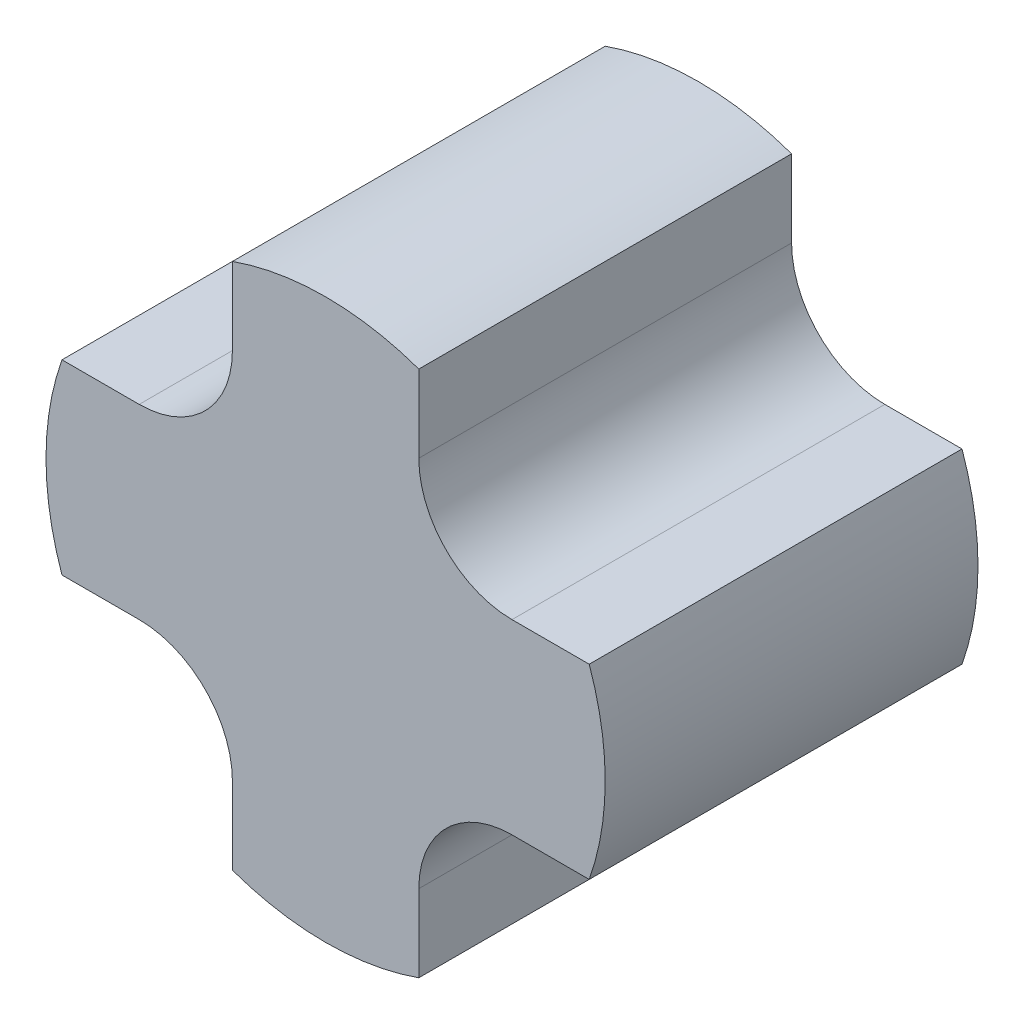
SolidWorks part; units mm, degrees
ref_plane "Front Plane" through (0, 0, 0) normal (1, 0, 0) x (0, 1, 0)
ref_plane "Top Plane" through (0, 0, 0) normal (0, 0, 1) x (0, 1, 0)
ref_plane "Right Plane" through (0, 0, 0) normal (0, 1, 0) x (-1, 0, 0)
sketch "Sketch1" plane through (0, 0, 0) normal (0, 0, 1) x (0, 1, 0)
  line L1 (-50, 141.4214) -> (-50, 0)
  line L2 (50, 141.4214) -> (50, 0)
  line L3 (-50, 0) -> (50, 0)
  arc A0 (50, 141.4214) -> (-50, 141.4214) centre (0, 0) ccw
  point P1 (-46.9864, 140.328)
  point P3 (0, 0)
  point P6 (50, 0)
  point P9 (-50, -34.7177)
  dimension "D1" = 150
  dimension "D2" = 100
extrude "Boss-Extrude1" add sketch "Sketch1" along normal blind 200
ref_axis "Axis1" through (0, 0, -10) along (0, 0, 1)
pattern_circular "CirPattern1" count 4 over 360 about axis through (0, 0, -10) along (0, 0, 1) of bodies 101
combine bodies "Combine1" bodies to combine 101 102 103 104
fillet "Fillet1" radius 50 4 edges at (50, 50, 100) (50, -50, 100) (-50, 50, 100) (-50, -50, 100)
